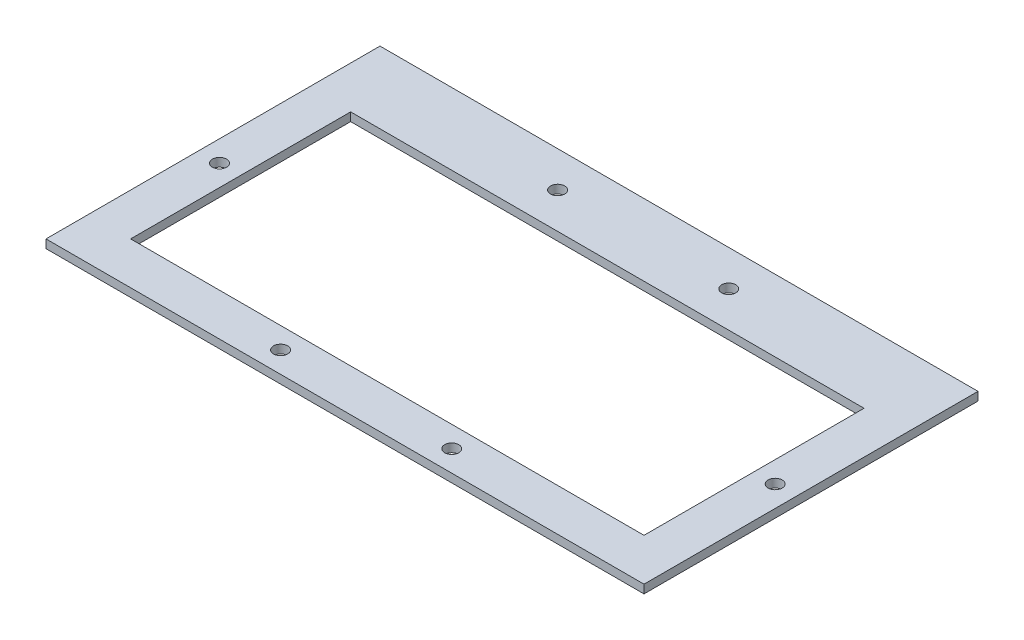
SolidWorks part; units mm, degrees
ref_plane "Front Plane" through (0, 0, 0) normal (0, 0, 1) x (1, 0, 0)
ref_plane "Top Plane" through (0, 0, 0) normal (0, 1, 0) x (1, 0, 0)
ref_plane "Right Plane" through (0, 0, 0) normal (1, 0, 0) x (0, 0, -1)
sketch "Sketch1" plane through (0, 0, 0) normal (0, 1, 0) x (1, 0, 0)
  line L0 (0, 0) -> (15, 0)
  line L1 (15, 0) -> (15, -78)
  line L2 (15, -78) -> (197, -78)
  line L3 (197, -78) -> (197, 0)
  line L4 (197, 0) -> (212, 0)
  line L5 (212, 0) -> (212, -93)
  line L6 (212, -93) -> (0, -93)
  line L7 (0, -93) -> (0, 0)
  line L8 (15, -78) -> (15, -93) construction
  line L9 (15, -85.5) -> (75.6667, -85.5) construction
  line L10 (75.6667, -85.5) -> (136.3333, -85.5) construction
  line L11 (136.3333, -85.5) -> (197, -85.5) construction
  line L13 (0, 0) -> (212, 0)
  line L14 (0, 0) -> (0, 25.4)
  line L15 (0, 25.4) -> (212, 25.4)
  line L16 (212, 0) -> (212, 25.4)
  line L17 (106, -78) -> (106, 0) construction
  line L18 (-20, -29) -> (0, -29)
  line L19 (-20, -29) -> (-20, -49)
  line L20 (-20, -49) -> (0, -49)
  line L21 (0, -29) -> (0, -49)
  line L22 (-20, -29) -> (0, -49) construction
  line L23 (-20, -49) -> (0, -29) construction
  line L24 (96, -113) -> (116, -113)
  line L25 (96, -113) -> (96, -93)
  line L26 (96, -93) -> (116, -93)
  line L27 (116, -113) -> (116, -93)
  line L28 (96, -113) -> (116, -93) construction
  line L29 (96, -93) -> (116, -113) construction
  line L30 (232, -49) -> (212, -29) construction
  line L31 (232, -29) -> (212, -49) construction
  line L32 (196.8585, -39) -> (-49769.383, -39) construction
  line L33 (232, -49) -> (212, -49)
  line L34 (232, -29) -> (212, -29)
  line L35 (232, -29) -> (232, -49)
  circle A0 centre (7.5, -39) radius 2.5
  circle A1 centre (204.5, -39) radius 2.5
  circle A3 centre (75.6667, -85.5) radius 2.5
  circle A4 centre (136.3333, -85.5) radius 2.5
  circle A5 centre (136.3333, 12.7) radius 2.5
  circle A6 centre (75.6667, 12.7) radius 2.5
  circle A7 centre (-10, -39) radius 3.175
  circle A8 centre (106, -103) radius 3.175
  circle A9 centre (222, -39) radius 3.175
  point P9 (15, -39)
  point P10 (106, -78)
  point P17 (15, -85.5)
  point P18 (7.5, 0)
  point P25 (204.5, 0)
  point P34 (-10, -39)
  point P39 (106, -103)
  point P59 (0, 12.7)
  dimension "D5" = 5
  dimension "D6" = 6.35
  dimension "D1" = 182
  dimension "D2" = 78
  dimension "D3" = 15
  dimension "D4" = 15
  dimension "D7" = 20
  dimension "D8" = 20
  dimension "D9" = 25.4
extrude "Boss-Extrude3" [suppressed] add sketch "Sketch1" along normal blind 3 contours L7 L6 L5 L4 L3 L2 L1 L0 A4 A3 A1 A0 | L19 L20 L7 L18 A7 | L24 L27 L6 L25 A8 | L35 L34 L5 L33 A9
extrude "Boss-Extrude4" add sketch "Sketch1<5>" along normal blind 3 contours L4 L16 L15 L14 L0 L13 A5 A6 | L7 L6 L5 L4 L3 L2 L1 L0 A4 A3 A1 A0 region at (106, 0, -12.7) region at (7.5, 0, 2.315)
sketch "Sketch1<5>" plane through (0, 0, 0) normal (0, 1, 0) x (1, 0, 0) same geometry as "Sketch1"
